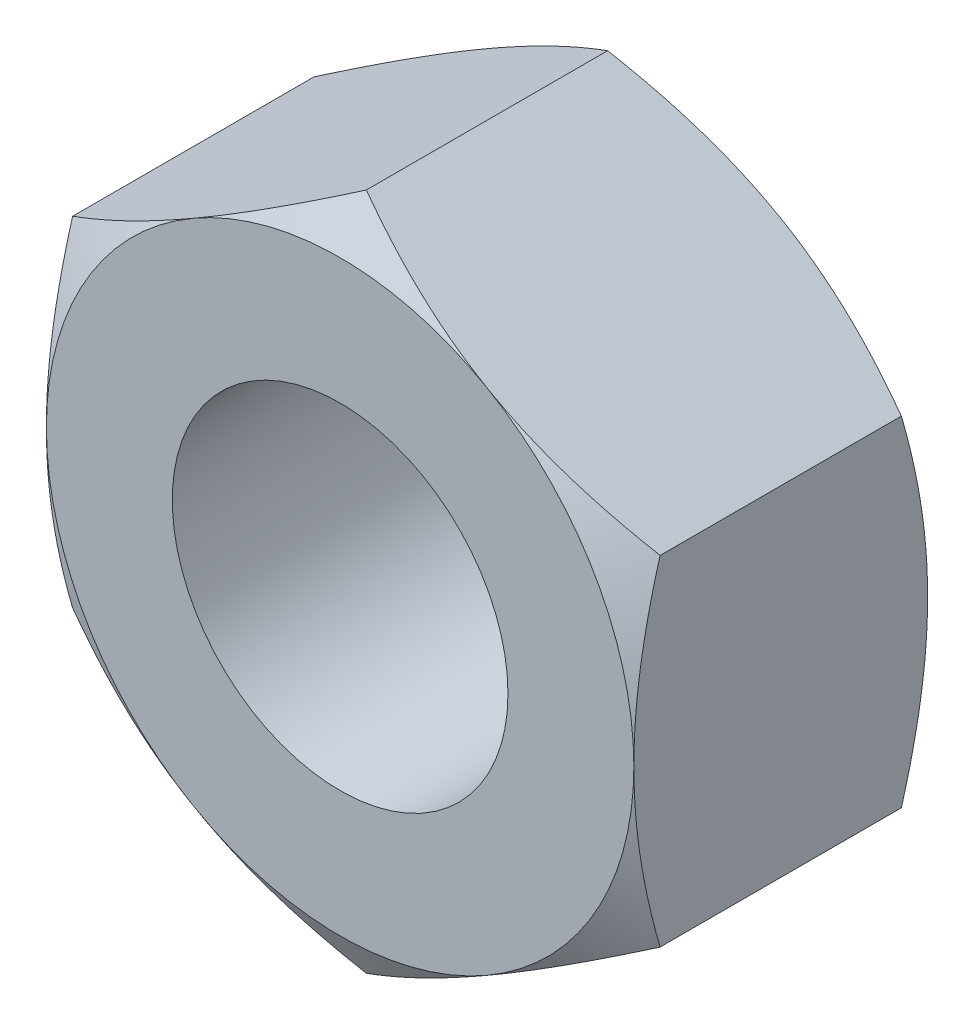
SolidWorks part; units mm, degrees
ref_plane "Front" through (0, 0, 0) normal (0, 0, 1) x (1, 0, 0)
ref_plane "Top" through (0, 0, 0) normal (0, 1, 0) x (1, 0, 0)
ref_plane "Right" through (0, 0, 0) normal (1, 0, 0) x (0, 0, -1)
sketch "Sketch1" plane through (0, 0, 0) normal (0, 0, 1) x (1, 0, 0)
  line L1 (-5.5562, 3.2079) -> (-5.5562, -3.2079)
  line L2 (-5.5562, -3.2079) -> (0, -6.4158)
  line L3 (0, -6.4158) -> (5.5562, -3.2079)
  line L4 (5.5562, -3.2079) -> (5.5562, 3.2079)
  line L5 (5.5562, 3.2079) -> (0, 6.4158)
  line L6 (0, 6.4158) -> (-5.5562, 3.2079)
  circle A0 centre (0, 0) radius 5.5562 construction
  circle A1 centre (0, 0) radius 3.175
  point P10 (0, 3.175)
  dimension "hex" = 11.1125
  dimension "dia" = 6.35
extrude "Extrude1" add sketch "Sketch1" along normal mid plane 5.5562
sketch "Sketch4" plane through (0, 0, -2.7781) normal (0, 0, -1) x (-1, 0, 0)
  circle A0 centre (0, 0) radius 3.175 construction
  circle A1 centre (0, 0) radius 3.175
curve "Helix/Spiral3" [suppressed] pitch 0.9071 height 6.6675 turns 7.35
sketch "Sketch3" plane through (0, 0, 0) normal (1, 0, 0) x (0, 0, -1)
  line L0 (2.7781, 3.175) -> (3.5719, 3.175)
  line L1 (3.5719, 3.175) -> (3.2317, 2.5858)
  line L2 (3.2317, 2.5858) -> (3.1183, 2.5858)
  line L3 (3.1183, 2.5858) -> (2.7781, 3.175)
  line L4 (2.9482, 2.8804) -> (3.4018, 2.8804) construction
  dimension "D1" = 60
  dimension "D2" = 0.4536
  dimension "D3" = 0.1134
sweep "Sweep1" [suppressed] add profiles "Sketch3" path "Helix/Spiral3"
sketch "Sketch6" [suppressed] plane through (0, 0, 0) normal (1, 0, 0) x (0, 0, -1)
  line L0 (-3.0049, 3.4018) -> (-2.5513, 2.9482)
  line L1 (-2.5513, 2.9482) -> (-2.5513, 0) construction
  line L2 (3.9291, 0) -> (-3.9291, 0) construction
  line L3 (-2.5513, 0) -> (-3.8899, 0)
  line L4 (-3.8899, 0) -> (-3.8899, 3.4018)
  line L5 (-3.8899, 3.4018) -> (-3.0049, 3.4018)
  line L6 (-2.5513, 2.9482) -> (0.3969, 0)
  line L7 (0.3969, 0) -> (-2.5513, 0)
  line L8 (-2.7781, -3.2079) -> (-2.7781, 3.2079) construction
  point P2 (-2.7781, 3.175)
  dimension "D2" = 0.4536
  dimension "D1" = 45
revolve "Cut-Revolve1" [suppressed] cut sketch "Sketch6" angle 360 about L3
sketch "Sketch7" plane through (0, 0, 2.7781) normal (0, 0, 1) x (1, 0, 0)
  circle A0 centre (0, 0) radius 5.5562 construction
  circle A1 centre (0, 0) radius 5.5562
extrude "Extrude2" cut sketch "Sketch7" against normal blind 25.4 draft 60 flip side to cut
mirror "Mirror1" about plane through (0, 0, 0) normal (0, 0, 1) of "Extrude2", "Cut-Revolve1"
sketch "Sketch8" [suppressed] plane through (0, 0, 2.7781) normal (0, 0, 1) x (1, 0, 0)
  line L0 (-2.2451, 2.2451) -> (0, 0) construction
  line L1 (0, -3.9291) -> (0, 3.9291) construction
  circle A0 centre (0, 0) radius 3.175 construction
  point P0 (-2.2451, 2.2451)
  dimension "D1" = 45
equation "\"D3@Helix/Spiral3\" = \"length@Extrude1\" * 1.2"
equation "\"D2@Sketch3\" = \"D4@Helix/Spiral3\" * .5"
equation "\"D3@Sketch3\" = \"D4@Helix/Spiral3\" * .125"
equation "\"D2@Sketch6\" = \"D4@Helix/Spiral3\" * .5"
